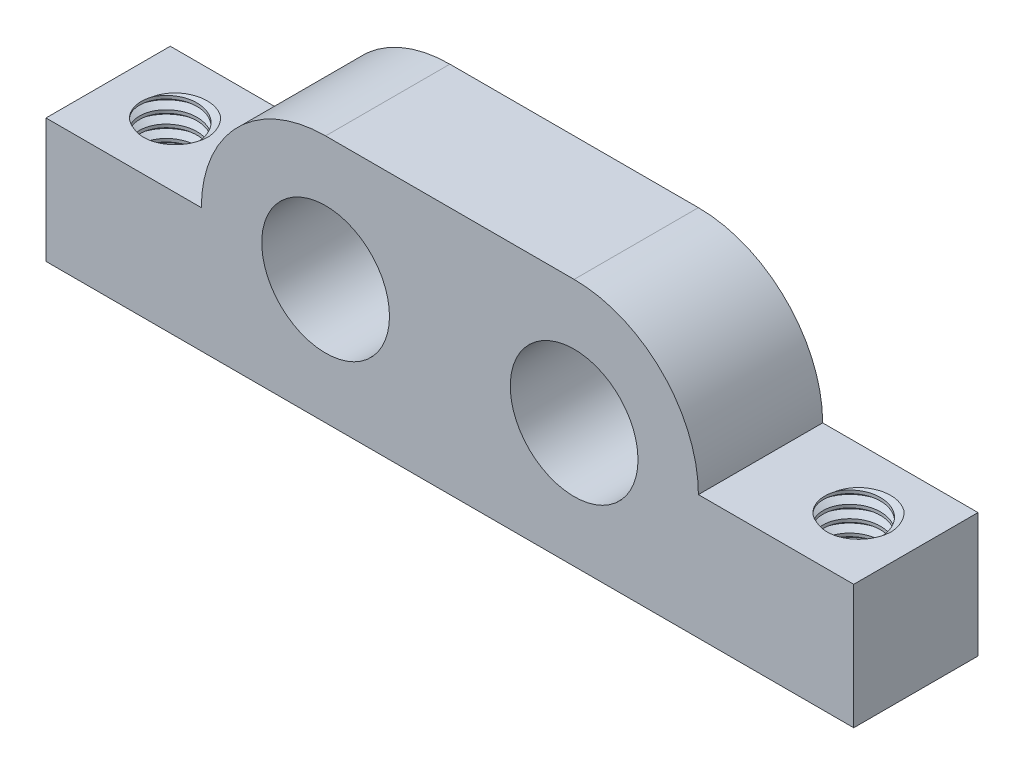
SolidWorks part; units mm, degrees
material "6061-T6 (SS)"
ref_plane "Front Plane" through (0, 0, 0) normal (0, 0, 1) x (1, 0, 0)
ref_plane "Top Plane" through (0, 0, 0) normal (0, 1, 0) x (1, 0, 0)
ref_plane "Right Plane" through (0, 0, 0) normal (1, 0, 0) x (0, 0, -1)
sketch "Sketch1" plane through (0, 0, 0) normal (0, 0, 1) x (1, 0, 0)
  line L0 (0, 0) -> (41.275, 0)
  line L1 (0, 0) -> (0, 6.35)
  line L2 (41.275, 0) -> (41.275, 6.35)
  line L3 (0, 6.35) -> (7.9375, 6.35)
  line L4 (41.275, 6.35) -> (33.3375, 6.35)
  line L6 (14.2875, 12.7) -> (26.9875, 12.7)
  arc A0 (7.9375, 6.35) -> (14.2875, 12.7) centre (14.2875, 6.35) cw
  arc A1 (33.3375, 6.35) -> (26.9875, 12.7) centre (26.9875, 6.35) ccw
  circle A2 centre (14.2875, 6.35) radius 3.2639
  circle A3 centre (26.9875, 6.35) radius 3.2639
  dimension "D2" = 6.35
  dimension "D3" = 6.35
  dimension "D6" = 6.5278
  dimension "D1" = 41.275
  dimension "D4" = 6.35
  dimension "D5" = 7.9375
extrude "Boss-Extrude1" add sketch "Sketch1" along normal blind 6.35
sketch "Sketch2" plane through (0, 6.35, 0) normal (0, 1, 0) x (1, 0, 0)
  line L0 (7.9375, 0) -> (0, 0) construction
  line L1 (0, -6.35) -> (0, 0) construction
  line L2 (41.275, -6.35) -> (41.275, 0) construction
  circle A0 centre (38.1, -3.175) radius 1.4732
  circle A1 centre (3.175, -3.175) radius 1.4732
  dimension "D3" = 2.9464
  dimension "D1" = 3.175
  dimension "D2" = 3.175
  dimension "D4" = 3.175
extrude "Cut-Extrude1" cut sketch "Sketch2" against normal up to next
sketch "Sketch3" plane through (0, 6.35, 0) normal (0, 1, 0) x (1, 0, 0)
  circle A0 centre (3.175, -3.175) radius 1.4732
thread "Thread1" pitch 0.635 method cut profile "Thread Profile1" start angle 0, offset 0.508, length 6.858, pitch 0.635, diameter 2.9464
ref_plane "Plane1" through (1.7018, 6.858, 3.175) normal (0, 0, 1) x (-1, 0, 0)
sketch "Thread Profile1" plane through (1.7018, 6.858, 3.175) normal (0, 0, 1) x (-1, 0, 0)
  line L0 (0, 0) -> (0, 0.635) construction
  line L1 (0, 0) -> (0.3437, 0.1984)
  line L2 (0.3437, 0.1984) -> (0.3437, 0.2778)
  line L3 (0.3437, 0.2778) -> (0, 0.4762)
  line L4 (0.3437, 0.2381) -> (0, 0.2381) construction
  line L11 (0, 0) -> (0, 0.4762)
  point P2 (0, 0)
  dimension "Pitch" = 0.635
  dimension "Profile_Angle" = 60
  dimension "Profile_Land" = 0.0794
  dimension "Profile_Height" = 0.3437
thread "Thread2" pitch 0.635 method cut profile "Thread Profile2" start angle 0, offset 0.508, length 6.858, pitch 0.635, diameter 2.9464
ref_plane "Plane2" through (36.6268, 6.858, 3.175) normal (0, 0, 1) x (-1, 0, 0)
sketch "Thread Profile2" plane through (36.6268, 6.858, 3.175) normal (0, 0, 1) x (-1, 0, 0)
  line L0 (0, 0) -> (0, 0.635) construction
  line L1 (0, 0) -> (0.3437, 0.1984)
  line L2 (0.3437, 0.1984) -> (0.3437, 0.2778)
  line L3 (0.3437, 0.2778) -> (0, 0.4762)
  line L4 (0.3437, 0.2381) -> (0, 0.2381) construction
  line L11 (0, 0) -> (0, 0.4762)
  point P2 (0, 0)
  dimension "Pitch" = 0.635
  dimension "Profile_Angle" = 60
  dimension "Profile_Land" = 0.0794
  dimension "Profile_Height" = 0.3437
